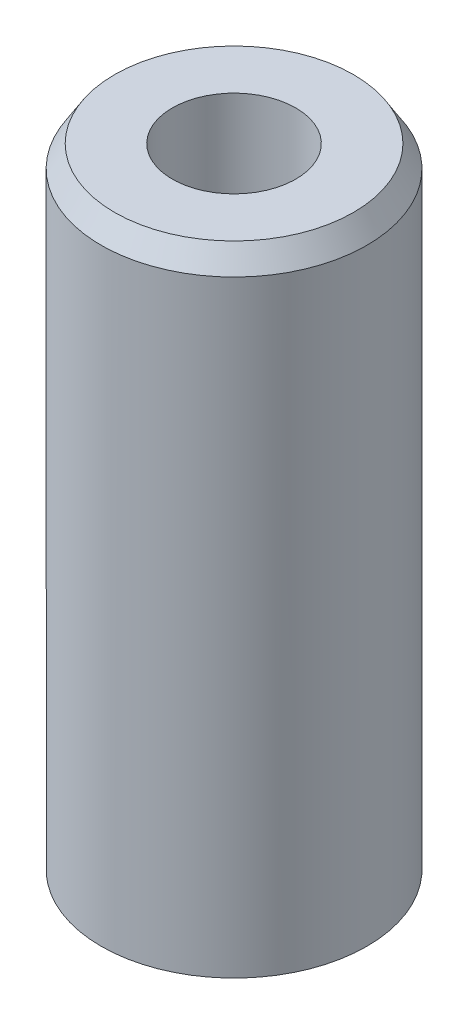
SolidWorks part; units mm, degrees
ref_plane "Front Plane" through (0, 0, 0) normal (0, 0, 1) x (1, 0, 0)
ref_plane "Top Plane" through (0, 0, 0) normal (0, 1, 0) x (1, 0, 0)
ref_plane "Right Plane" through (0, 0, 0) normal (1, 0, 0) x (0, 0, -1)
sketch "Sketch1" plane through (0, 0, 0) normal (0, 1, 0) x (1, 0, 0)
  circle A0 centre (0, 0) radius 20
  dimension "SHAFT_OD" = 40
extrude "Boss-Extrude1" add sketch "Sketch1" along normal blind 96.668
sketch "Sketch2" plane through (0, 0, 0) normal (0, 1, 0) x (1, 0, 0)
  circle A0 centre (0, 0) radius 9.2926
  dimension "BORE_D" = 18.5852
extrude "Cut-Extrude1" cut sketch "Sketch2" along normal through all
chamfer "Chamfer1" distance 3.2668 angle 31.798 2 edges at (0, 96.668, 20) (0, 0, 20) first distance on face at (0, 96.668, 20) first distance on face at (0, 0, 9.2926)
